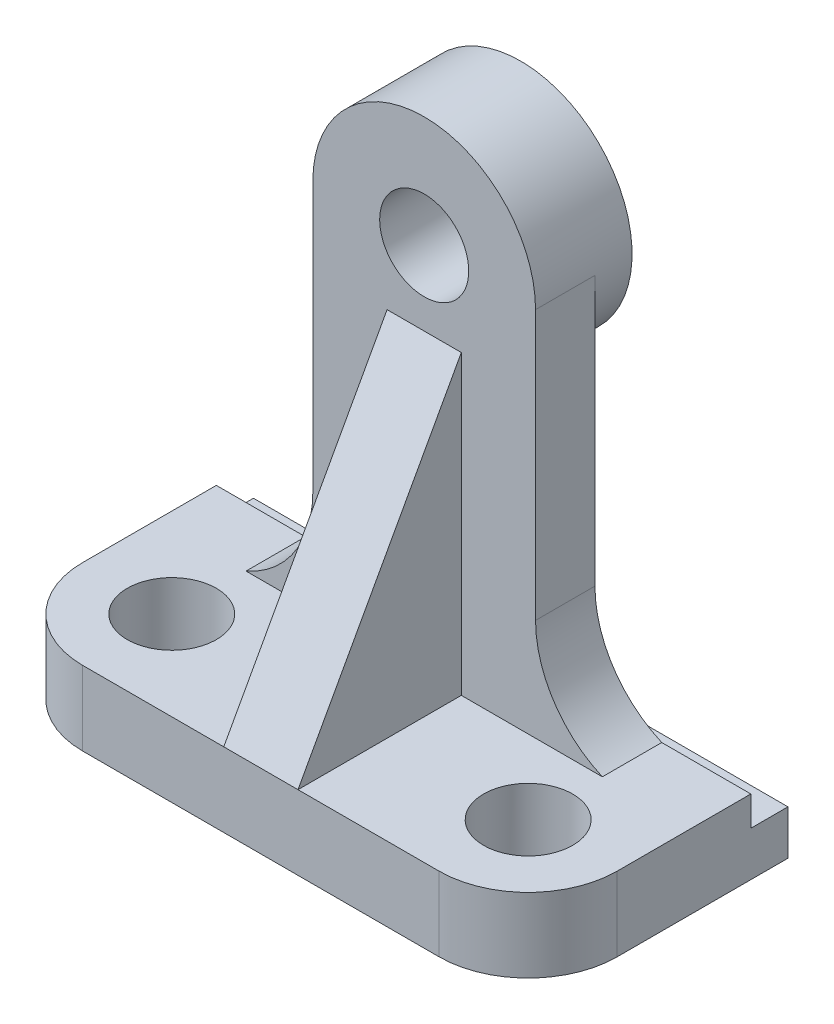
SolidWorks part; units mm, degrees
ref_plane "Front Plane" through (0, 0, 0) normal (0, 0, 1) x (1, 0, 0)
ref_plane "Top Plane" through (0, 0, 0) normal (0, 1, 0) x (1, 0, 0)
ref_plane "Right Plane" through (0, 0, 0) normal (1, 0, 0) x (0, 0, -1)
sketch "Sketch1" plane through (0, 0, 0) normal (0, 1, 0) x (1, 0, 0)
  line L0 (-31.5139, 0) -> (33.745, 0) construction
  line L1 (0, 30.0498) -> (0, -27.261) construction
  line L2 (-36, 17.5) -> (36, 17.5)
  line L3 (36, 17.5) -> (36, -5.5)
  line L4 (24, -17.5) -> (-24, -17.5)
  line L5 (-36, -5.5) -> (-36, 17.5)
  arc A0 (36, -5.5) -> (24, -17.5) centre (24, -5.5) cw
  arc A1 (-24, -17.5) -> (-36, -5.5) centre (-24, -5.5) cw
  point P11 (36, -17.5)
  point P14 (-36, -17.5)
  dimension "D3" = 12
  dimension "D1" = 35
  dimension "D2" = 72
extrude "Boss-Extrude1" add sketch "Sketch1" along normal blind 10
sketch "Sketch3" plane through (-36, 0, 0) normal (-1, 0, 0) x (0, 0, 1)
  line L0 (-17.5, 6) -> (-12.5, 6)
  line L1 (-17.5, 10) -> (-17.5, 0) construction
  line L2 (-12.5, 6) -> (-12.5, 10)
  line L3 (-17.5, 10) -> (5.5, 10) construction
  line L4 (-12.5, 10) -> (-17.5, 10)
  line L5 (-17.5, 10) -> (-17.5, 6)
  dimension "D1" = 6
  dimension "D2" = 5
extrude "Cut-Extrude1" cut sketch "Sketch3" against normal blind 74
sketch "Sketch4" plane through (0, 0, -12.5) normal (0, 0, -1) x (-1, 0, 0)
  line L0 (24, 10) -> (-24, 10) construction
  line L1 (15, 60) -> (15, 23.7477)
  line L2 (-15, 60) -> (-15, 23.7477)
  line L3 (24, 10) -> (-24, 10)
  arc A0 (15, 60) -> (-15, 60) centre (0, 60) ccw
  arc A1 (15, 23.7477) -> (24, 10) centre (30, 23.7477) ccw
  arc A2 (-15, 23.7477) -> (-24, 10) centre (-30, 23.7477) cw
  dimension "D1" = 30
  dimension "D3" = 15
  dimension "D2" = 50
extrude "Boss-Extrude2" add sketch "Sketch4" against normal blind 8
sketch "Sketch5" plane through (0, 0, -12.5) normal (0, 0, -1) x (-1, 0, 0)
  circle A0 centre (0, 60) radius 15
extrude "Boss-Extrude3" add sketch "Sketch5" along normal blind 5
sketch "Sketch6" plane through (0, 0, -17.5) normal (0, 0, -1) x (-1, 0, 0)
  circle A0 centre (0, 60) radius 6
  dimension "D1" = 12
extrude "Cut-Extrude2" cut sketch "Sketch6" against normal up to surface (13 mm away) up to face at (0, 33.3019, -4.5)
sketch "Sketch7" plane through (0, 0, 0) normal (1, 0, 0) x (0, 0, -1)
  line L0 (-17.5, 10) -> (4.5, 50)
  line L1 (4.5, 60) -> (4.5, 23.7477) construction
  dimension "D1" = 40
rib "Rib1" sketch "Sketch7" sketch "Sketch7" thickness 10 extrusion direction parallel to sketch draft on no parameters "D1"=10
sketch "Sketch8" plane through (0, 10, 0) normal (0, 1, 0) x (1, 0, 0)
  line L0 (-47.4452, -5.5) -> (43.5563, -5.5) construction
  line L1 (36, 17.5) -> (-36, 17.5) construction
  line L2 (0, 26.3893) -> (0, -29.1671) construction
  circle A0 centre (24, -5.5) radius 6
  circle A1 centre (-24, -5.5) radius 6
  dimension "D3" = 12
  dimension "D1" = 23
  dimension "D2" = 24
extrude "Cut-Extrude4" cut sketch "Sketch8" against normal blind 11
